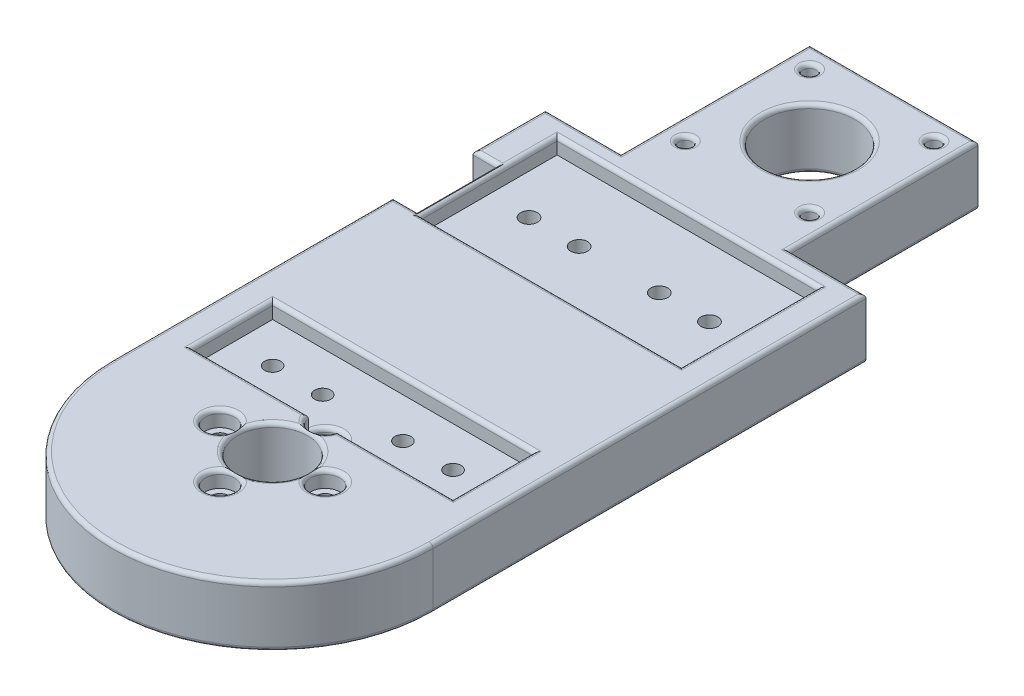
SolidWorks part; units mm, degrees
ref_plane "Ebene vorne" through (0, 0, 0) normal (0, 0, 1) x (1, 0, 0)
ref_plane "Ebene oben" through (0, 0, 0) normal (0, 1, 0) x (1, 0, 0)
ref_plane "Ebene rechts" through (0, 0, 0) normal (1, 0, 0) x (0, 0, -1)
sketch "Skizze1" plane through (0, 0, 0) normal (0, 1, 0) x (1, 0, 0)
  line L0 (-25.9794, -40) -> (25.9794, -40) construction
  line L2 (-40, 0) -> (-40, 108)
  line L4 (40, 0) -> (40, 108)
  line L5 (-40, 0) -> (40, 108) construction
  line L6 (-40, 108) -> (40, 0) construction
  line L9 (-40, 108) -> (-40, 78)
  line L12 (-40, 108) -> (40, 108)
  line L13 (-21.0848, 155) -> (20.9152, 113) construction
  line L21 (-21.0848, 108) -> (20.9152, 108)
  line L22 (-21.0848, 108) -> (-21.0848, 155)
  line L23 (-21.0848, 155) -> (20.9152, 155)
  line L24 (20.9152, 108) -> (20.9152, 155)
  line L25 (20.9152, 155) -> (-21.0848, 113) construction
  line L26 (0, 17.5) -> (0, 8.75) construction
  circle A0 centre (0, 0) radius 40
  circle A2 centre (-0.0848, 134) radius 11.3
  circle A3 centre (-15.5848, 149.5) radius 1.65
  circle A4 centre (15.4152, 149.5) radius 1.65
  circle A5 centre (15.4152, 118.5) radius 1.65
  circle A6 centre (-15.5848, 118.5) radius 1.65
  circle A7 centre (0, 0) radius 8.75
  circle A8 centre (0, 0) radius 17.5
  circle A17 centre (0, 13.125) radius 2.1
  circle A18 centre (13.125, 0) radius 2.1
  circle A19 centre (0, -13.125) radius 2.1
  circle A20 centre (-13.125, 0) radius 2.1
  point P7 (0, 54)
  point P11 (0, -40)
  point P31 (-0.0848, 134)
  point P36 (0, 13.125)
  point P44 (0, 0)
  point P52 (0, 0)
  dimension "D1" = 80
  dimension "D5" = 148
  dimension "D4" = 42
  dimension "D6" = 4
  dimension "D7" = 35
  dimension "D8" = 4
  dimension "D9" = 3.3
  dimension "D11" = 17.5
  dimension "D2" = 42
  dimension "D3" = 5
extrude "Aufsatz-Linear austragen1" add sketch "Skizze1" along normal blind 15 contours L12 L24 L23 L22 A6 A5 A4 A3 A2 | A0 L4 L12 L2 | A0 A8 | A8 A20 A19 A18 A17 A7
sketch "Skizze5" plane through (0, 15, 0) normal (0, 1, 0) x (1, 0, 0)
  line L0 (40, 0) -> (40, 108) construction
  line L1 (-25, 69.5) -> (40, 69.5)
  line L2 (-25, 69.5) -> (-25, 32.5)
  line L3 (-25, 32.5) -> (40, 32.5)
  line L4 (40, 69.5) -> (40, 32.5)
  line L5 (-25, 69.5) -> (40, 32.5) construction
  line L6 (-25, 32.5) -> (40, 69.5) construction
  line L7 (0, 0) -> (0, 22.5) construction
  line L8 (-25, 32.5) -> (40, 32.5)
  line L13 (20.9152, 108) -> (40, 108) construction
  line L14 (-32.5, 12.5) -> (32.5, 12.5)
  line L15 (-32.5, 12.5) -> (-32.5, 32.5)
  line L16 (-32.5, 32.5) -> (32.5, 32.5)
  line L17 (32.5, 12.5) -> (32.5, 32.5)
  line L18 (-32.5, 12.5) -> (32.5, 32.5) construction
  line L19 (-32.5, 32.5) -> (32.5, 12.5) construction
  point P4 (7.5, 51)
  point P13 (0, 22.5)
  dimension "D1" = 20
  dimension "D2" = 37
  dimension "D3" = 65
  dimension "D4" = 38.5
extrude "Schnitt-Linear austragen3" cut sketch "Skizze5" against normal blind 4 contours L14 L17 L3 L16 L15 region at (0, 15, -22.5)
sketch "Skizze6" plane through (0, 11, 0) normal (0, 1, 0) x (1, 0, 0)
  line L0 (-32.5, 22.5) -> (32.5, 22.5) construction
  line L1 (32.5, 12.5) -> (32.5, 32.5) construction
  line L3 (0, 22.5) -> (0, 3.2798) construction
  line L5 (32.5, 12.5) -> (32.5, 32.5) construction
  circle A0 centre (10, 22.5) radius 2
  circle A1 centre (-10, 22.5) radius 2
  circle A2 centre (22.5, 22.5) radius 2
  circle A3 centre (-22.5, 22.5) radius 2
  dimension "D2" = 4
  dimension "D3" = 4
  dimension "D1" = 10
  dimension "D4" = 12.5
extrude "Schnitt-Linear austragen4" cut sketch "Skizze6" against normal blind 11
sketch "Skizze14" plane through (0, 15, 0) normal (0, 1, 0) x (1, 0, 0)
  line L0 (-40, 108) -> (-40, 90) construction
  line L1 (-40, 0) -> (-40, 108) construction
  line L2 (-40, 108) -> (-21.0848, 108) construction
  line L4 (-40, 90) -> (-34, 90)
  line L5 (-40, 90) -> (-40, 70)
  line L6 (-40, 70) -> (-34, 70)
  line L7 (-34, 90) -> (-34, 70)
  line L8 (-40, 90) -> (-34, 70) construction
  line L9 (-40, 70) -> (-34, 90) construction
  point P9 (-37, 80)
  dimension "D1" = 20
  dimension "D2" = 18
  dimension "D3" = 6
extrude "Schnitt-Linear austragen11" cut sketch "Skizze14" against normal blind 15 contours L5 L4 L7 L6
sketch "Skizze15" plane through (-34, 0, 0) normal (-1, 0, 0) x (0, 0, 1)
  line L0 (-90, 0) -> (-90, 15) construction
  line L1 (-70, 0) -> (-70, 15) construction
  circle A1 centre (-84.5, 7.5) radius 2.25
  circle A2 centre (-75, 7.5) radius 2.25
  dimension "D1" = 4.5
  dimension "D2" = 4.5
  dimension "D3" = 9.5
  dimension "D4" = 5.5
  dimension "D5" = 5
extrude "Schnitt-Linear austragen12" cut sketch "Skizze15" against normal blind 6
sketch "Skizze19" plane through (0, 15, 0) normal (0, 1, 0) x (1, 0, 0)
  line L0 (0, 0) -> (-0.0848, 134) construction
  line L2 (-32.5547, 69.5) -> (32.4453, 69.5)
  line L3 (-32.5547, 69.5) -> (-32.5547, 103.5)
  line L4 (-32.5547, 103.5) -> (32.4453, 103.5)
  line L5 (32.4453, 69.5) -> (32.4453, 103.5)
  line L6 (-32.5547, 69.5) -> (32.4453, 103.5) construction
  line L7 (-32.5547, 103.5) -> (32.4453, 69.5) construction
  line L8 (20.9152, 108) -> (40, 108) construction
  point P4 (-0.0547, 86.5)
  dimension "D1" = 65
  dimension "D2" = 34
  dimension "D3" = 4.5
extrude "Schnitt-Linear austragen15" cut sketch "Skizze19" against normal blind 4
sketch "Skizze21" plane through (0, 11, 0) normal (0, 1, 0) x (1, 0, 0)
  line L1 (-0.0548, 84) -> (-0.0548, 95.2298) construction
  line L4 (32.4453, 69.5) -> (32.4453, 103.5) construction
  line L5 (-32.5547, 86.5) -> (32.4453, 86.5) construction
  line L6 (-32.5547, 103.5) -> (-32.5547, 69.5) construction
  circle A0 centre (22.4453, 86.5) radius 2.1
  circle A1 centre (9.9453, 86.5) radius 2.1
  circle A2 centre (-22.5548, 86.5) radius 2.1
  circle A3 centre (-10.0548, 86.5) radius 2.1
  dimension "D1" = 10
  dimension "D2" = 12.5
extrude "Schnitt-Linear austragen16" cut sketch "Skizze21" against normal blind 11
sketch "Skizze22" plane through (0, 0, 0) normal (0, -1, 0) x (1, 0, 0)
  line L0 (0, -84) -> (0, -79.7713) construction
  circle A0 centre (-22.5548, -86.5) radius 3.65
  circle A1 centre (-10.0548, -86.5) radius 3.65
  circle A2 centre (10.0548, -86.5) radius 3.65
  circle A3 centre (22.5548, -86.5) radius 3.65
  circle A4 centre (-22.5548, -86.5) radius 2.1 construction
  circle A5 centre (-10.0548, -86.5) radius 2.1 construction
  circle A6 centre (-22.5, -22.5) radius 3.65
  circle A7 centre (-10, -22.5) radius 3.65
  circle A8 centre (10, -22.5) radius 3.65
  circle A9 centre (22.5, -22.5) radius 3.65
  dimension "D1" = 7.3
  dimension "D2" = 7.3
  dimension "D3" = 7.3
  dimension "D4" = 7.3
extrude "Schnitt-Linear austragen17" cut sketch "Skizze22" against normal blind 4
sketch "Skizze23" plane through (0, 0, 0) normal (0, -1, 0) x (1, 0, 0)
  circle A0 centre (-15.5848, -118.5) radius 3.2
  circle A1 centre (-0.0848, -134) radius 11.3
  circle A2 centre (15.4152, -118.5) radius 3.2
  circle A3 centre (15.4152, -149.5) radius 3.2
  circle A4 centre (-15.5848, -149.5) radius 3.2
  point P6 (15.4152, -120.5)
  point P15 (-0.0848, -134)
  dimension "D1" = 4
  dimension "D2" = 6.4
extrude "Schnitt-Linear austragen18" cut sketch "Skizze23" against normal blind 3
sketch "Sketch5" plane through (0, 15, 0) normal (0, 1, 0) x (1, 0, 0)
  circle A12 centre (-13.125, 0) radius 3.65
  circle A13 centre (-13.125, 0) radius 2.1 construction
  circle A14 centre (0, 13.125) radius 3.65
  circle A15 centre (13.125, 0) radius 3.65
  circle A16 centre (0, -13.125) radius 3.65
  point P10 (0, 0)
  point P14 (0, 0)
  dimension "D1" = 7.3
  dimension "D2" = 4
extrude "Cut-Extrude3" cut sketch "Sketch5" against normal blind 4
sketch "Skizze24" plane through (0, 11, 0) normal (0, 1, 0) x (1, 0, 0)
  circle A0 centre (0, 13.125) radius 3.65
  dimension "D1" = 7.3
extrude "Schnitt-Linear austragen19" cut sketch "Skizze24" against normal blind 4
fillet "Verrundung1" radius 1 62 edges at (0, 15, 8.75) (-0.0848, 15, -122.7) (-15.5848, 15, -147.85) (15.4152, 15, -147.85) (15.4152, 15, -116.85) (-15.5848, 15, -116.85) (-34, 15, -80) (-37, 15, -90) (-40, 15, -99) (-30.5424, 15, -108) (-21.0848, 15, -131.5) (-0.0848, 15, -155) (20.9152, 15, -131.5) (30.4576, 15, -108) (40, 15, -54) (0, 15, 40) (-40, 15, -35) (-37, 15, -70) (-0.0547, 15, -103.5) (-32.5547, 15, -86.5) (-0.0547, 15, -69.5) (32.4453, 15, -86.5) (0, 15, 16.775) (13.125, 15, 3.65) (18.048, 15, -12.5) (32.5, 15, -22.5) (0, 15, -32.5) (-32.5, 15, -22.5) (-18.048, 15, -12.5) (0, 15, -9.475) (-13.125, 15, 3.65) (0, 0, 8.75) (0, 0, -11.025) (13.125, 0, 2.1) (0, 0, 15.225) (-13.125, 0, 2.1) (0, 0, 40) (40, 0, -54) (30.4576, 0, -108) (20.9152, 0, -131.5) (-0.0848, 0, -155) (-21.0848, 0, -131.5) (-30.5424, 0, -108) (-40, 0, -99) (-37, 0, -90) (-34, 0, -80) (-37, 0, -70) (-40, 0, -35) (-0.0848, 0, -122.7) (-22.5548, 0, -90.15) (22.5, 0, -18.85) (10, 0, -18.85) (-10, 0, -26.15) (-10.0548, 0, -90.15) (10.0548, 0, -82.85) (22.5548, 0, -82.85) (-22.5, 0, -26.15) (-15.5848, 0, -121.7) (15.4152, 0, -121.7) (15.4152, 0, -152.7) (-15.5848, 0, -152.7) (0, 11, -16.775)
